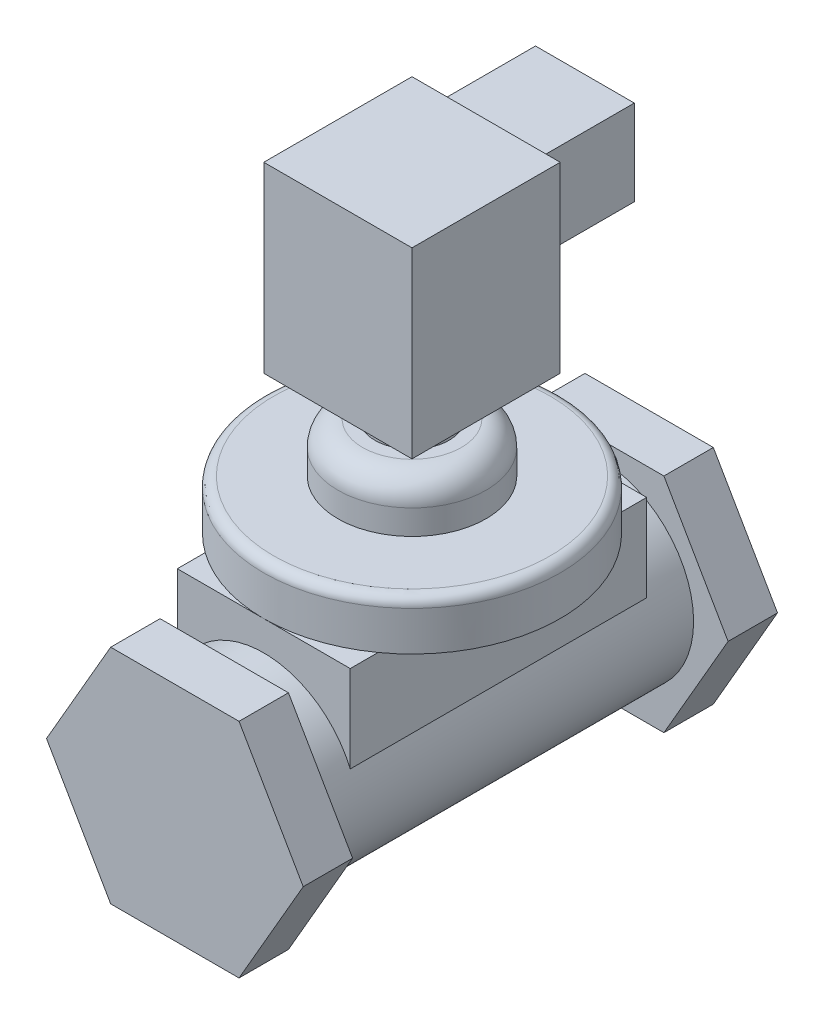
SolidWorks part; units mm, degrees
ref_plane "Спереди" through (0, 0, 0) normal (0, 0, 1) x (1, 0, 0)
ref_plane "Сверху" through (0, 0, 0) normal (0, 1, 0) x (1, 0, 0)
ref_plane "Справа" through (0, 0, 0) normal (1, 0, 0) x (0, 0, -1)
sketch "Эскиз1" plane through (0, 0, 0) normal (0, 0, 1) x (1, 0, 0)
  line L0 (25.9808, 0) -> (0, 0) construction
  line L1 (-25.9808, 0) -> (-12.9904, -22.5)
  line L2 (-12.9904, -22.5) -> (12.9904, -22.5)
  line L3 (12.9904, -22.5) -> (25.9808, 0)
  line L4 (25.9808, 0) -> (12.9904, 22.5)
  line L5 (12.9904, 22.5) -> (-12.9904, 22.5)
  line L6 (-12.9904, 22.5) -> (-25.9808, 0)
  circle A0 centre (0, 0) radius 22.5 construction
  dimension "D1" = 45
extrude "Вытянуть1" add sketch "Эскиз1" along normal blind 10
sketch "Эскиз2" plane through (0, 0, 0) normal (0, 0, -1) x (-1, 0, 0)
  circle A0 centre (0, 0) radius 19
  dimension "D1" = 38
extrude "Вытянуть2" add sketch "Эскиз2" along normal blind 76
sketch "Эскиз3" plane through (0, 0, -76) normal (0, 0, -1) x (-1, 0, 0)
  line L1 (25.9808, 0) -> (12.9904, 22.5)
  line L2 (12.9904, 22.5) -> (-12.9904, 22.5)
  line L3 (-12.9904, 22.5) -> (-25.9808, 0)
  line L4 (-25.9808, 0) -> (-12.9904, -22.5)
  line L5 (-12.9904, -22.5) -> (12.9904, -22.5)
  line L6 (12.9904, -22.5) -> (25.9808, 0)
  circle A0 centre (0, 0) radius 22.5 construction
extrude "Вытянуть3" add sketch "Эскиз3" along normal blind 10
sketch "Эскиз4" plane through (0, 0, 0) normal (0, 1, 0) x (1, 0, 0)
  line L1 (-17.5, 8) -> (17.5, 8)
  line L2 (-17.5, 8) -> (-17.5, 68)
  line L3 (-17.5, 68) -> (17.5, 68)
  line L4 (17.5, 8) -> (17.5, 68)
  line L5 (-12.9904, -10) -> (-25.9808, -10) construction
  dimension "D1" = 60
  dimension "D2" = 18
  dimension "D3" = 35
  dimension "D4" = 17.5
extrude "Вытянуть4" add sketch "Эскиз4" along normal blind 25
sketch "Эскиз5" plane through (0, 25, 0) normal (0, 1, 0) x (1, 0, 0)
  line L0 (-12.9904, -10) -> (-25.9808, -10) construction
  line L1 (0, 76) -> (0, 0) construction
  circle A0 centre (0, 38) radius 30
  dimension "D1" = 60
  dimension "D2" = 48
extrude "Вытянуть9" add sketch "Эскиз5" along normal blind 10
sketch "Эскиз6" plane through (0, 35, 0) normal (0, 1, 0) x (1, 0, 0)
  circle A0 centre (0, 38) radius 15
  dimension "D1" = 30
extrude "Вытянуть10" add sketch "Эскиз6" along normal blind 10
fillet "Скругление1" radius 5 1 edges at (0, 45, -23)
sketch "Эскиз7" plane through (0, 45, 0) normal (0, 1, 0) x (1, 0, 0)
  circle A0 centre (0, 38) radius 7.5
  dimension "D1" = 15
extrude "Вытянуть11" add sketch "Эскиз7" along normal blind 8
sketch "Эскиз8" plane through (0, 53, 0) normal (0, 1, 0) x (1, 0, 0)
  line L1 (15, 53) -> (-15, 53)
  line L2 (15, 53) -> (15, 23)
  line L3 (15, 23) -> (-15, 23)
  line L4 (-15, 53) -> (-15, 23)
  circle A0 centre (0, 38) radius 7.5 construction
  dimension "D1" = 30
  dimension "D3" = 15
  dimension "D2" = 30
  dimension "D4" = 15
extrude "Вытянуть12" add sketch "Эскиз8" along normal blind 37
fillet "Скругление4" radius 2 1 edges at (0, 35, -8)
sketch "Эскиз9" plane through (0, 0, -53) normal (0, 0, -1) x (-1, 0, 0)
  line L0 (-15, 90) -> (-15, 53) construction
  line L1 (-10, 87.8782) -> (10, 87.8782)
  line L2 (-10, 87.8782) -> (-10, 70.5698)
  line L3 (-10, 70.5698) -> (10, 70.5698)
  line L4 (10, 87.8782) -> (10, 70.5698)
  line L5 (15, 90) -> (15, 53) construction
  dimension "D1" = 5
  dimension "D2" = 5
extrude "Бобышка-Вытянуть1" add sketch "Эскиз9" along normal blind 20
ref_axis "Ось1" through (0, 0, -76) along (0, 0, 1)
